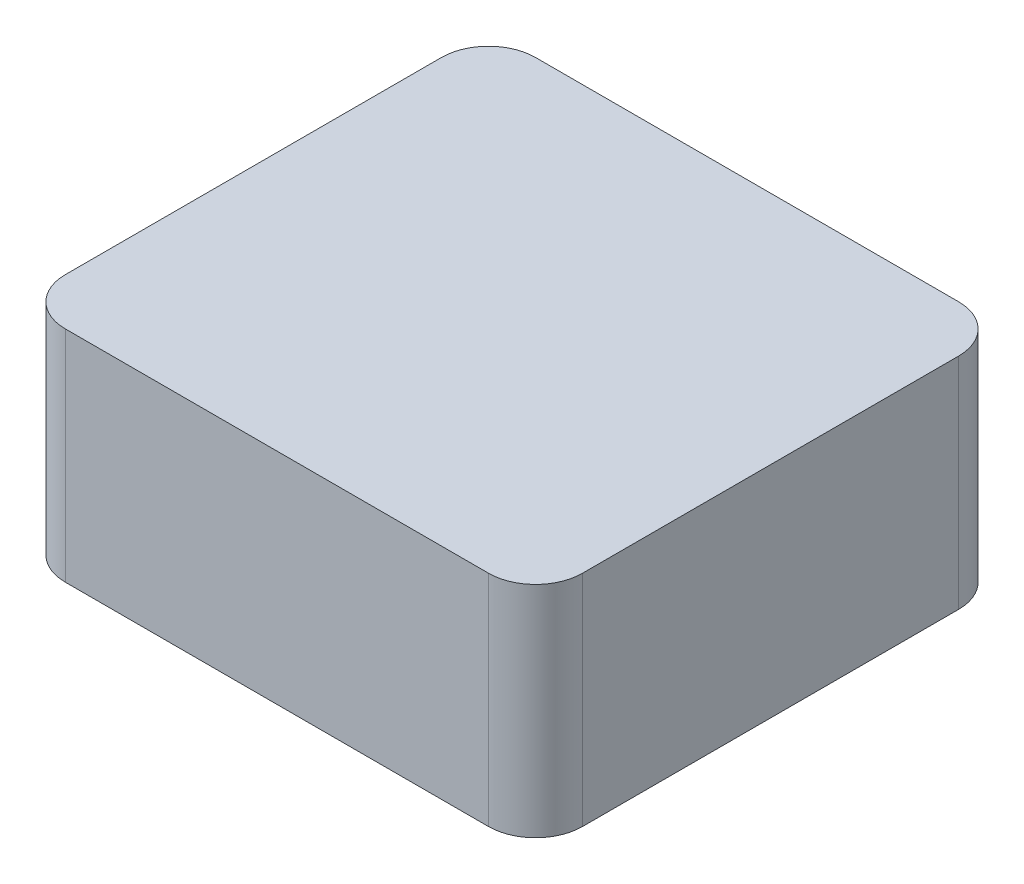
SolidWorks part; units mm, degrees
ref_plane "Plan de face" through (0, 0, 0) normal (0, 0, 1) x (1, 0, 0)
ref_plane "Plan de dessus" through (0, 0, 0) normal (0, 1, 0) x (1, 0, 0)
ref_plane "Plan de droite" through (0, 0, 0) normal (1, 0, 0) x (0, 0, -1)
sketch "Esquisse1" plane through (0, 0, 0) normal (0, 1, 0) x (1, 0, 0)
  line L1 (-16.5, 15) -> (16.5, 15)
  line L2 (-16.5, 15) -> (-16.5, -15)
  line L3 (-16.5, -15) -> (16.5, -15)
  line L4 (16.5, 15) -> (16.5, -15)
  point P4 (0, 15)
  point P6 (16.5, 0)
  dimension "D1" = 33
  dimension "D2" = 30
extrude "Boss.-Extru.1" add sketch "Esquisse1" along normal blind 7 and the other way blind 7
fillet "Congé1" radius 3 4 edges at (-16.5, 0, -15) (16.5, 0, -15) (16.5, 0, 15) (-16.5, 0, 15)
